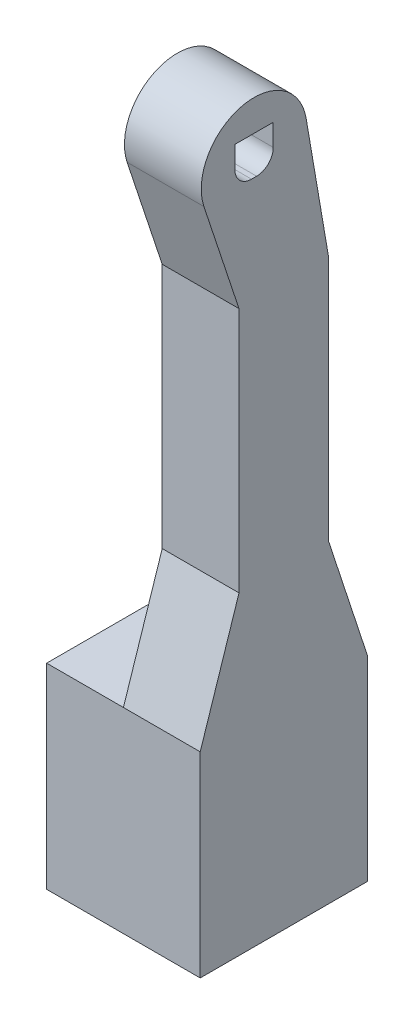
SolidWorks part; units mm, degrees
ref_plane "Front Plane" through (0, 0, 0) normal (0, 0, 1) x (1, 0, 0)
ref_plane "Top Plane" through (0, 0, 0) normal (0, 1, 0) x (1, 0, 0)
ref_plane "Right Plane" through (0, 0, 0) normal (1, 0, 0) x (0, 0, -1)
sketch "Sketch1" plane through (0, 0, 0) normal (1, 0, 0) x (0, 0, -1)
  line L0 (-3, 9.82) -> (-3, 0)
  line L1 (-3, 0) -> (-6.5301, 0)
  line L2 (-6.5301, 0) -> (-6.5301, 9.82)
  line L3 (-6.5301, 15.3053) -> (-3.4983, 24.5417)
  line L4 (-3.4983, 24.5417) -> (-3.4983, 43.7787)
  line L5 (0, 0) -> (0, 50000) construction
  line L6 (3.4983, 24.5417) -> (3.4983, 43.7787)
  line L7 (6.5301, 15.3053) -> (3.4983, 24.5417)
  line L8 (6.5301, 0) -> (6.5301, 9.82)
  line L9 (3, 0) -> (6.5301, 0)
  line L10 (3, 9.82) -> (3, 0)
  line L11 (-3, 9.82) -> (3, 9.82)
  line L12 (-2.5244, 52.0529) -> (-2.1244, 52.0529) construction
  line L13 (-2.5244, 53.3529) -> (-2.1244, 53.3529) construction
  line L14 (-3.8244, 55.0529) -> (-3.8244, 53.3529) construction
  line L15 (-0.8244, 53.3529) -> (-0.8244, 55.0529) construction
  line L16 (-0.8244, 55.0529) -> (-3.8244, 55.0529) construction
  line L17 (-3.8244, 55.0529) -> (-0.8244, 55.0529) construction
  line L18 (-2.5244, 52.0529) -> (-2.1244, 52.0529)
  line L19 (-3.8244, 55.0529) -> (-3.8244, 53.3529)
  line L20 (-0.8244, 53.3529) -> (-0.8244, 55.0529)
  line L21 (-0.8244, 55.0529) -> (-3.8244, 55.0529)
  line L22 (-3.8244, 55.0529) -> (-0.8244, 55.0529)
  line L23 (-3.4983, 43.7787) -> (-6.2409, 52.0551)
  line L24 (3.4983, 43.7787) -> (1.7425, 54.0483)
  line L25 (6.5301, 9.82) -> (6.5301, 15.3053)
  line L26 (-6.5301, 9.82) -> (-6.5301, 15.3053)
  line L27 (-6.5301, 9.82) -> (-3, 9.82)
  line L28 (3, 9.82) -> (6.5301, 9.82)
  line L29 (3, 0) -> (-3, 0)
  line L30 (6.5301, 15.3053) -> (-6.5301, 15.3053)
  arc A0 (-2.1244, 52.0529) -> (-0.8244, 53.3529) centre (-2.1244, 53.3529) ccw construction
  arc A1 (-3.8244, 53.3529) -> (-2.5244, 52.0529) centre (-2.5244, 53.3529) ccw construction
  arc A2 (-2.1244, 52.0529) -> (-0.8244, 53.3529) centre (-2.1244, 53.3529) ccw
  arc A3 (-3.8244, 53.3529) -> (-2.5244, 52.0529) centre (-2.5244, 53.3529) ccw
  arc A4 (-6.2409, 52.0551) -> (1.7425, 54.0483) centre (-2.3244, 53.3529) cw
  dimension "D1" = 6
  dimension "D2" = 9.82
extrude "Boss-Extrude2" add sketch "Sketch1" against normal blind 6 contours L28 L10 L9 L8 | L27 L2 L1 L0 | L25 L30 L26 L27 L11 L28 region at (0, 12.5626, 0) region at (0, 4.91, 4.7651) region at (0, 4.91, -4.7651)
extrude "Boss-Extrude3" add sketch "Sketch1<4>" along normal blind 6 contours L29 L10 L11 L0 | L27 L2 L1 L0 | L28 L10 L9 L8 | L25 L30 L26 L27 L11 L28 | A4 L23 L4 L3 L30 L7 L6 L24 A3 L19 L21 L20 A2 L18 region at (0, 4.91, 0) region at (0, 12.5626, 0) region at (0, 4.91, 4.7651) region at (0, 4.91, -4.7651) region at (0, 34.5288, 0.4207)
sketch "Sketch1<4>" plane through (0, 0, 0) normal (1, 0, 0) x (0, 0, -1) same geometry as "Sketch1"
